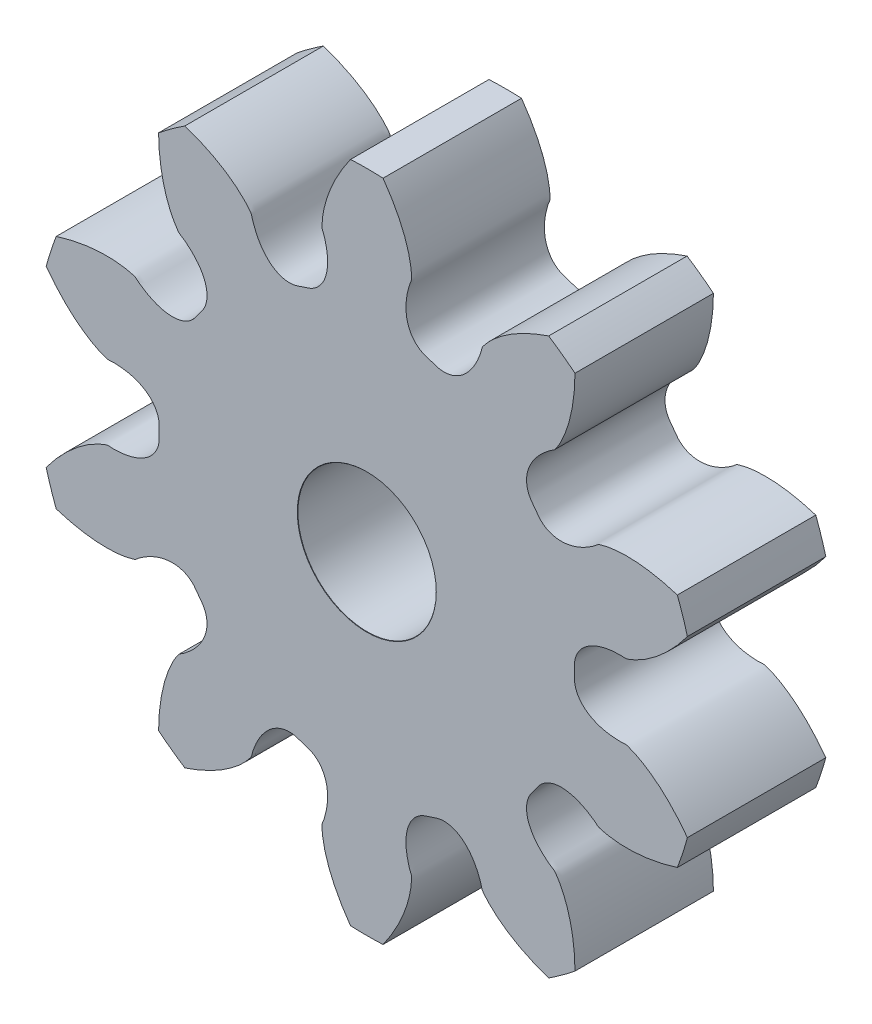
SolidWorks part; units mm, degrees
ref_plane "Front Plane" through (0, 0, 0) normal (0, 0, 1) x (1, 0, 0)
ref_plane "Top Plane" through (0, 0, 0) normal (0, 1, 0) x (1, 0, 0)
ref_plane "Right Plane" through (0, 0, 0) normal (1, 0, 0) x (0, 0, -1)
ref_axis "Axis1" through (0, 0, 55) along (0, 0, -1)
sketch "SketchRevolveSpur01" plane through (0, 0, 0) normal (1, 0, 0) x (0, 0, -1)
  line L0 (0, 0) -> (1, 0) construction
  line L1 (-2.5, 0) -> (-2.5, 12)
  line L2 (-2.5, 12) -> (2.5, 12)
  line L3 (2.5, 12) -> (2.5, 0)
  line L4 (2.5, 0) -> (-2.5, 0)
  dimension "Side1" = 2.5
  dimension "OutsideRadius" = 12
  dimension "Side2" = 2.5
revolve "Spur01" add sketch "SketchRevolveSpur01" angle 360 about L0
sketch "SketchToothSpur01" plane through (0, 0, 0) normal (0, 0, 1) x (1, 0, 0)
  arc A0 (11.6557, 3.249) -> (11.6557, -3.249) centre (0, 0) cw
  spline S0 degree 3 poles (11.6557, -3.249) (11.5423, -3.0893) (11.3677, -2.8624) (11.1235, -2.583) (10.948, -2.3979) (10.7762, -2.2308) (10.6093, -2.0811) (10.4483, -1.9481) (10.2945, -1.8312) (10.1487, -1.7294) (10.0119, -1.6419) (9.8851, -1.5678) (9.769, -1.5061) (9.6644, -1.4561) (9.5722, -1.4158) (9.4742, -1.38) (9.3515, -1.3286) (9.2141, -1.3558) (9.0897, -1.351) (8.9912, -1.3478) (8.8951, -1.3404) (8.8013, -1.3301) (8.7098, -1.3167) (8.6206, -1.3002) (8.5337, -1.2806) (8.4492, -1.2579) (8.3671, -1.232) (8.2873, -1.2028) (8.2098, -1.1702) (8.1347, -1.1342) (8.0621, -1.0944) (7.9919, -1.0508) (7.9244, -1.0029) (7.8597, -0.9507) (7.7981, -0.8936) (7.74, -0.8313) (7.686, -0.7636) (7.6368, -0.6902) (7.5934, -0.6111) (7.5566, -0.5264) (7.5278, -0.4366) (7.5078, -0.3426) (7.4995, -0.2566) (7.4964, -0.1421) (7.5027, 0) (7.4964, 0.1421) (7.4995, 0.2566) (7.5078, 0.3426) (7.5278, 0.4366) (7.5566, 0.5264) (7.5934, 0.6111) (7.6368, 0.6902) (7.686, 0.7636) (7.74, 0.8313) (7.7981, 0.8936) (7.8597, 0.9507) (7.9244, 1.0029) (7.9919, 1.0508) (8.0621, 1.0944) (8.1347, 1.1342) (8.2098, 1.1702) (8.2873, 1.2028) (8.3671, 1.232) (8.4492, 1.2579) (8.5337, 1.2806) (8.6206, 1.3002) (8.7098, 1.3167) (8.8013, 1.3301) (8.8951, 1.3404) (8.9912, 1.3478) (9.0897, 1.351) (9.2141, 1.3558) (9.3515, 1.3286) (9.4742, 1.38) (9.5722, 1.4158) (9.6644, 1.4561) (9.769, 1.5061) (9.8851, 1.5678) (10.0119, 1.6419) (10.1487, 1.7294) (10.2945, 1.8312) (10.4483, 1.9481) (10.6093, 2.0811) (10.7762, 2.2308) (10.948, 2.3979) (11.1235, 2.583) (11.3677, 2.8624) (11.5423, 3.0893) (11.6557, 3.249) knots 0 0 0 0 0.05171 0.075523 0.097976 0.119068 0.138799 0.15717 0.17418 0.189829 0.204117 0.217044 0.228611 0.238817 0.247662 0.255146 0.266488 0.281932 0.290791 0.299458 0.307939 0.316243 0.324379 0.332357 0.340187 0.347883 0.35546 0.362932 0.370318 0.37764 0.384918 0.392178 0.399448 0.406756 0.414133 0.42161 0.429217 0.436977 0.444912 0.453029 0.461324 0.469778 0.478358 0.484106 0.5 0.515894 0.521642 0.530222 0.538676 0.546971 0.555088 0.563023 0.570783 0.57839 0.585867 0.593244 0.600552 0.607822 0.615082 0.62236 0.629682 0.637068 0.64454 0.652117 0.659813 0.667643 0.675621 0.683757 0.692061 0.700542 0.709209 0.718068 0.733512 0.744854 0.752338 0.761183 0.771389 0.782956 0.795883 0.810171 0.82582 0.84283 0.861201 0.880932 0.902024 0.924477 0.94829 1 1 1 1
extrude "ToothExtrudeCutSpur01" cut sketch "SketchToothSpur01" against normal blind 2.5 and the other way blind 2.5
pattern_circular "PatternSpur01" count 10 every 36 about axis through (0, 0, 55) along (0, 0, -1) of "ToothExtrudeCutSpur01"
sketch "BoreRevolveSketch" plane through (0, 0, 0) normal (1, 0, 0) x (0, 0, -1)
  line L0 (0, 0) -> (1, 0) construction
  line L1 (-2.5, 0) -> (2.5, 0)
  line L2 (2.5, 0) -> (2.5, 2.51)
  line L3 (2.5, 2.51) -> (2.49, 2.5)
  line L4 (2.49, 2.5) -> (-2.49, 2.5)
  line L5 (-2.49, 2.5) -> (-2.5, 2.51)
  line L6 (-2.5, 2.51) -> (-2.5, 0)
  dimension "BoreSide1" = 2.5
  dimension "TaperSide1" = 2.51
  dimension "Chamfer1X" = 0.01
  dimension "Chamfer1Y" = 0.01
  dimension "BoreSide2" = 2.5
  dimension "TaperSide2" = 2.51
revolve "BoreRevolveCut" cut sketch "BoreRevolveSketch" angle 360 about L0
sketch "AuxiliarySketchSpur01" plane through (0, 0, 0) normal (0, 0, 1) x (1, 0, 0)
  circle A0 centre (0, 0) radius 10 construction
  circle A1 centre (0, 0) radius 9.3969 construction
  circle A2 centre (0, 0) radius 9.7869 construction
  circle A3 centre (0, 0) radius 12 construction
  circle A4 centre (0, 0) radius 7.5 construction
  dimension "PitchDiameter" = 20
  dimension "BaseDiameter" = 18.7939
  dimension "FormDiameter" = 19.5737
  dimension "MajorDiameter" = 24
  dimension "MinorDiameter" = 15
